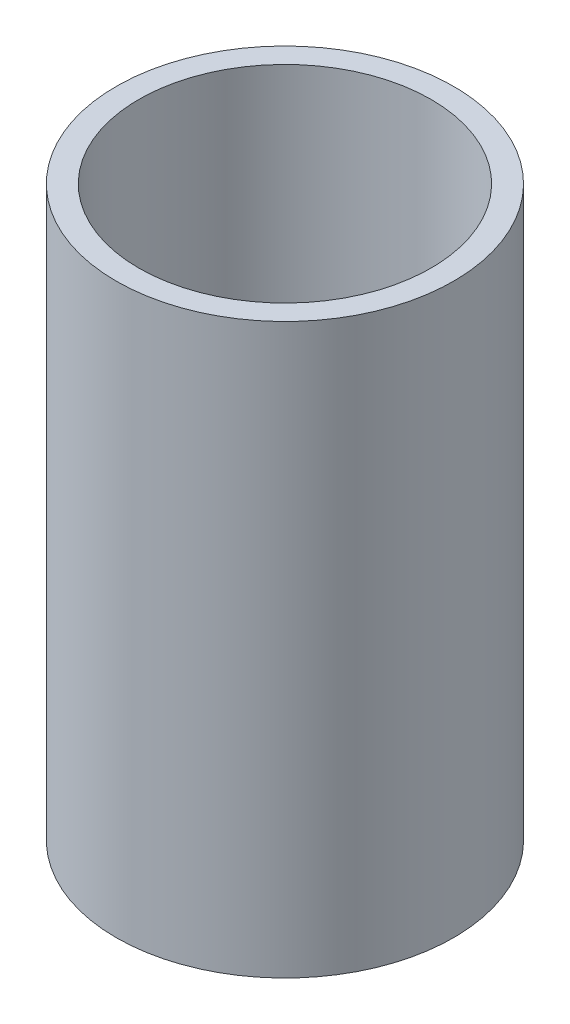
SolidWorks part; units mm, degrees
ref_plane "Front Plane" through (0, 0, 0) normal (0, 0, 1) x (1, 0, 0)
ref_plane "Top Plane" through (0, 0, 0) normal (0, 1, 0) x (1, 0, 0)
ref_plane "Right Plane" through (0, 0, 0) normal (1, 0, 0) x (0, 0, -1)
sketch "Sketch1" plane through (0, 0, 0) normal (0, 1, 0) x (1, 0, 0)
  circle A0 centre (0, 0) radius 37.5
  dimension "SLEEVE_OD" = 75
extrude "Boss-Extrude1" add sketch "Sketch1" along normal blind 126.3784
sketch "Sketch2" plane through (0, 0, 0) normal (0, 1, 0) x (1, 0, 0)
  circle A0 centre (0, 0) radius 32.482
  dimension "BORE_D" = 64.964
extrude "Cut-Extrude1" cut sketch "Sketch2" along normal through all
chamfer "Chamfer1" distance 2.1229 angle 60.604 rebuild error yes
